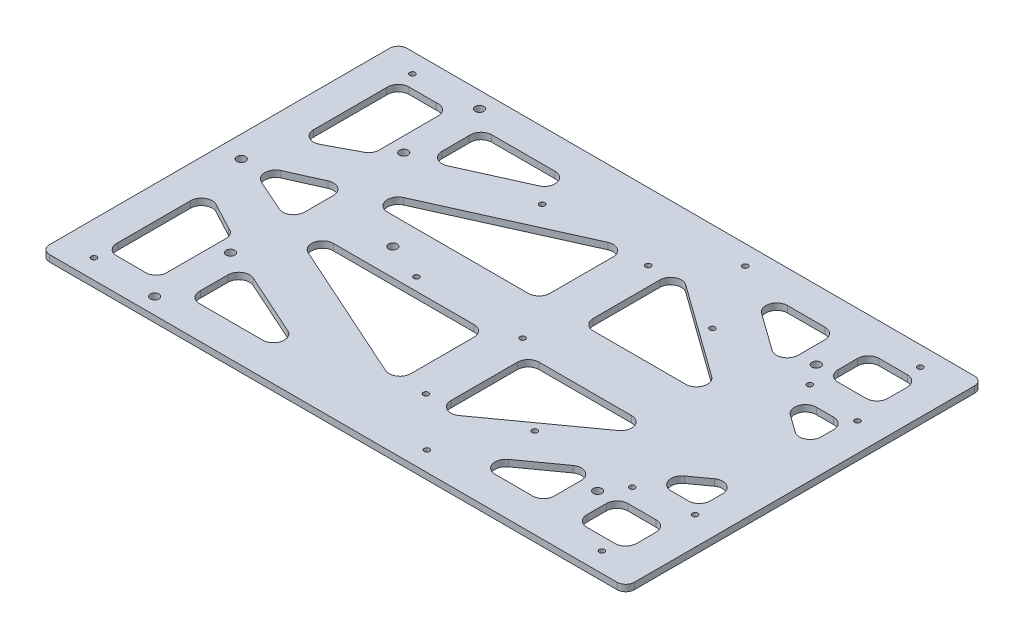
SolidWorks part; units mm, degrees
material "Aleación 1060"
ref_plane "Alzado" through (0, 0, 0) normal (0, 0, 1) x (1, 0, 0)
ref_plane "Planta" through (0, 0, 0) normal (0, 1, 0) x (1, 0, 0)
ref_plane "Vista lateral" through (0, 0, 0) normal (1, 0, 0) x (0, 0, -1)
sketch "Croquis1" plane through (0, 0, 0) normal (0, 1, 0) x (1, 0, 0)
  line L1 (135, -82.5) -> (-135, -82.5)
  line L2 (135, -82.5) -> (135, 82.5)
  line L3 (135, 82.5) -> (-135, 82.5)
  line L4 (-135, -82.5) -> (-135, 82.5)
  line L5 (135, -82.5) -> (-135, 82.5) construction
  line L6 (135, 82.5) -> (-135, -82.5) construction
  point P0 (0, 0)
  dimension "D1" = 165
  dimension "D2" = 270
extrude "Saliente-Extruir1" add sketch "Croquis1" along normal blind 3
fillet "Redondeo1" radius 4 4 edges at (-135, 1.5, -82.5) (135, 1.5, -82.5) (135, 1.5, 82.5) (-135, 1.5, 82.5)
sketch "Croquis2" plane through (0, 3, 0) normal (0, 1, 0) x (1, 0, 0)
  line L0 (131, 82.5) -> (-131, 82.5) construction
  line L1 (135, -78.5) -> (135, 78.5) construction
  circle A0 centre (90, 50.5) radius 2
  dimension "D1" = 4
  dimension "D2" = 32
  dimension "D3" = 45
extrude "Cortar-Extruir1" cut sketch "Croquis2" against normal through all
mirror "Simetría1" about plane through (0, 0, 0) normal (0, 0, 1) of "Cortar-Extruir1"
sketch "Croquis3" plane through (0, 3, 0) normal (0, 1, 0) x (1, 0, 0)
  line L0 (-135, 78.5) -> (-135, -78.5) construction
  line L1 (131, 82.5) -> (-131, 82.5) construction
  line L2 (-135, 0) -> (-113.8944, 0) construction
  circle A0 centre (-90, 75) radius 2
  circle A1 centre (-90, -75) radius 2
  dimension "D1" = 4
  dimension "D2" = 45
  dimension "D3" = 7.5
extrude "Cortar-Extruir2" cut sketch "Croquis3" against normal through all
sketch "Croquis4" plane through (0, 3, 0) normal (0, 1, 0) x (1, 0, 0)
  line L0 (0, 82.5) -> (0, -82.5) construction
  line L1 (131, 82.5) -> (-131, 82.5) construction
  line L2 (-131, -82.5) -> (131, -82.5) construction
  line L3 (-135, 0) -> (135, 0) construction
  line L4 (-135, 78.5) -> (-135, -78.5) construction
  line L5 (135, -78.5) -> (135, 78.5) construction
  line L6 (0, -82.5) -> (131, -82.5) construction
  line L7 (135, -82.5) -> (135, 78.5) construction
  line L8 (131, 82.5) -> (0, 82.5) construction
  line L9 (115, 67.5) -> (102.5, 67.5)
  line L12 (110.2817, 0) -> (2.6409, -64.5845) construction
  line L13 (131, 67.5) -> (-131, 67.5) construction
  line L14 (4.9275, 63.2125) -> (110.2817, 0) construction
  line L15 (15, 10) -> (75.5635, 10)
  line L16 (131, 82.5) -> (-131, 82.5) construction
  line L17 (15, -10) -> (75.5635, -10)
  line L18 (10, 51.3381) -> (10, 15)
  line L19 (17.5725, 55.6256) -> (78.136, 19.2875)
  line L20 (78.136, -19.2875) -> (17.5725, -55.6256)
  line L24 (52.1339, 58.2125) -> (74.9275, 44.5363)
  line L29 (15.2174, 80.3624) -> (149.1548, 0) construction
  line L30 (90, 50.5) -> (90, 67.5) construction
  line L31 (149.1548, 0) -> (12.9308, -81.7344) construction
  line L32 (99.9275, 29.5363) -> (112.4275, 22.0363)
  line L34 (82.5, 62.5) -> (82.5, 48.8238)
  line L36 (97.5, 62.5) -> (97.5, 33.8238)
  line L37 (120, 26.3238) -> (120, 62.5)
  line L38 (77.5, 67.5) -> (54.7063, 67.5)
  line L39 (10, -15) -> (10, -51.3381)
  arc A3 (120, 62.5) -> (115, 67.5) centre (115, 62.5) ccw
  arc A4 (120, 26.3238) -> (112.4275, 22.0363) centre (115, 26.3238) cw
  arc A5 (99.9275, 29.5363) -> (97.5, 33.8238) centre (102.5, 33.8238) cw
  arc A6 (102.5, 67.5) -> (97.5, 62.5) centre (102.5, 62.5) ccw
  arc A7 (10, -51.3381) -> (17.5725, -55.6256) centre (15, -51.3381) ccw
  arc A9 (10, 51.3381) -> (17.5725, 55.6256) centre (15, 51.3381) cw
  arc A10 (75.5635, 10) -> (78.136, 19.2875) centre (75.5635, 15) ccw
  arc A11 (75.5635, -10) -> (78.136, -19.2875) centre (75.5635, -15) cw
  arc A12 (15, 10) -> (10, 15) centre (15, 15) cw
  arc A13 (15, -10) -> (10, -15) centre (15, -15) ccw
  arc A14 (82.5, 48.8238) -> (74.9275, 44.5363) centre (77.5, 48.8238) cw
  arc A15 (77.5, 67.5) -> (82.5, 62.5) centre (77.5, 62.5) cw
  arc A16 (52.1339, 58.2125) -> (54.7063, 67.5) centre (54.7063, 62.5) cw
  point P44 (97.5, 30.9929)
  point P64 (10, -10)
  dimension "D5" = 33.6762
  dimension "D6" = 5
  dimension "D7" = 5
  dimension "D13" = 5
  dimension "D14" = 5
  dimension "D15" = 5
  dimension "D16" = 22.0363
  dimension "D2" = 5
  dimension "D4" = 15
  dimension "D8" = 15
  dimension "D10" = 10
  dimension "D11" = 10
  dimension "D12" = 10
  dimension "D3" = 20
  dimension "D1" = 15
extrude "Cortar-Extruir3" [suppressed] cut sketch "Croquis4" against normal through all
mirror "Simetría4" [suppressed] about plane through (0, 0, 0) normal (1, 0, 0)
sketch "Croquis5" plane through (0, 3, 0) normal (0, 1, 0) x (1, 0, 0)
  line L0 (135, -78.5) -> (135, 78.5) construction
  line L1 (-131, -82.5) -> (131, -82.5) construction
  line L2 (131, 82.5) -> (-131, 82.5) construction
  circle A0 centre (-119.5, 73.5) radius 1.75
  circle A1 centre (34.2, 73.5) radius 1.75
  circle A2 centre (115, 73.5) radius 1.75
  circle A3 centre (115, -73.5) radius 1.75
  circle A4 centre (34.2, -73.5) radius 1.75
  circle A5 centre (-119.5, -73.5) radius 1.75
  point P0 (-119.5, 73.5)
  point P3 (34.2, 73.5)
  point P6 (115, 73.5)
  point P9 (115, -73.5)
  point P12 (34.2, -73.5)
  point P15 (-119.5, -73.5)
  dimension "D1" = 20
  dimension "D2" = 80.8
  dimension "D3" = 153.7
  dimension "D4" = 9
  dimension "D5" = 9
hole_wizard "Taladro roscado M31" positions "Croquis5" profile "Croquis6" tap size "M3" standard "ISO"
sketch "Croquis6" plane through (-119.5, 3, -73.5) normal (1, 0, 0) x (0, 0, 1)
  line L0 (0, 0) -> (0, 9.2511)
  line L1 (0, 9.2511) -> (1.25, 8.5)
  line L2 (1.25, 8.5) -> (1.25, 0)
  line L5 (1.25, 0) -> (0, 0)
  line L10 (0, 9.2511) -> (-1.25, 8.5) construction
  line L11 (0, -6.35) -> (0, 107.95) construction
  dimension "Diámetro de perforador para roscar" = 2.5
  dimension "Profundidad de perforador para roscar" = 8.5
  dimension "Ángulo de perforador" = 118
cosmetic thread "Rosca de taladro1" parameters "D1"=6, "D2"=3
cosmetic thread "Rosca de taladro2" parameters "D1"=6, "D2"=3
cosmetic thread "Rosca de taladro3" parameters "D1"=6, "D2"=3
cosmetic thread "Rosca de taladro4" parameters "D1"=6, "D2"=3
cosmetic thread "Rosca de taladro5" parameters "D1"=6, "D2"=3
cosmetic thread "Rosca de taladro6" parameters "D1"=6, "D2"=3
mirror "Simetría5" [suppressed] about plane through (0, 0, 0) normal (0, 0, 1)
mirror "Simetría7" [suppressed] about plane through (0, 0, 0) normal (1, 0, 0)
mirror "Simetría8" [suppressed] about plane through (0, 0, 0) normal (1, 0, 0)
sketch "Croquis9" plane through (0, 3, 0) normal (0, 1, 0) x (1, 0, 0)
  line L0 (-131, -82.5) -> (131, -82.5) construction
  line L2 (-135, 78.5) -> (-135, -78.5) construction
  line L4 (131, 82.5) -> (-131, 82.5) construction
  circle A0 centre (-125, 0) radius 2
  circle A1 centre (-90, 40) radius 2
  circle A2 centre (-55, 0) radius 2
  circle A3 centre (-90, -40) radius 2
  point P1 (-90, -40)
  point P3 (-55, 0)
  dimension "D1" = 4
  dimension "D5" = 10
  dimension "D3" = 82.5
  dimension "D6" = 45
  dimension "D2" = 42.5
  dimension "D4" = 80
  dimension "D7" = 42.5
extrude "Cortar-Extruir4" cut sketch "Croquis9" against normal blind 4
sketch "Croquis10" plane through (0, 3, 0) normal (0, 1, 0) x (1, 0, 0)
  circle A0 centre (0, 0) radius 2
  circle A1 centre (0, 60.1959) radius 2
  circle A2 centre (0, -65.3126) radius 2
  dimension "D1" = 4
extrude "Cortar-Extruir5" [suppressed] cut sketch "Croquis10" against normal through all
sketch "Croquis11" plane through (0, 3, 0) normal (0, 1, 0) x (1, 0, 0)
  point P0 (-37.4183, 51.3035)
  point P1 (11.5817, 51.3035)
  point P3 (11.5817, -6.6965)
  point P5 (-37.4183, -6.6965)
  point P17 (-37.4183, 51.3035)
  point P19 (-37.4183, -6.6965)
  point P21 (11.5817, -6.6965)
  point P23 (11.5817, 51.3035)
hole_wizard "Taladro roscado M33" positions "Croquis11" profile "Croquis13" tap size "M3" standard "ISO"
sketch "Croquis13" plane through (-37.4183, 3, -51.3035) normal (1, 0, 0) x (0, 0, 1)
  line L0 (0, 0) -> (0, 9.2511)
  line L1 (0, 9.2511) -> (1.25, 8.5)
  line L2 (1.25, 8.5) -> (1.25, 0)
  line L5 (1.25, 0) -> (0, 0)
  line L10 (0, 9.2511) -> (-1.25, 8.5) construction
  line L11 (0, -6.35) -> (0, 107.95) construction
  dimension "Diámetro de perforador para roscar" = 2.5
  dimension "Profundidad de perforador para roscar" = 8.5
  dimension "Ángulo de perforador" = 118
cosmetic thread "Rosca de taladro35" parameters "D1"=6, "D2"=3
cosmetic thread "Rosca de taladro36" parameters "D1"=6, "D2"=3
cosmetic thread "Rosca de taladro37" parameters "D1"=6, "D2"=3
cosmetic thread "Rosca de taladro38" parameters "D1"=6, "D2"=3
sketch "Croquis14" plane through (0, 3, 0) normal (0, 1, 0) x (1, 0, 0)
  line L0 (-135, 0) -> (135, 0) construction
  line L1 (-135, 78.5) -> (-135, -78.5) construction
  line L2 (135, -78.5) -> (135, 78.5) construction
  line L3 (0, 82.5) -> (0, -82.5) construction
  line L5 (-131, -82.5) -> (131, -82.5) construction
  line L6 (-120, 28.3988) -> (-120, 62.0179)
  line L7 (-100.1523, 30.6318) -> (-112.6523, 23.9842)
  line L8 (-96.7551, 61.9356) -> (-96.7099, 34.9641)
  line L9 (131, 67.5) -> (-131, 67.5)
  line L10 (120, 67.5) -> (-120, 67.5) construction
  line L11 (-115, 67.5) -> (-102.5, 67.5)
  line L12 (-120, 78.5) -> (-120, -78.5)
  line L13 (-120, 67.5) -> (-120, -67.5) construction
  line L14 (-77.0591, 67.5) -> (-47.6094, 67.5)
  line L15 (-131, -67.5) -> (131, -67.5)
  line L16 (-120, -67.5) -> (120, -67.5) construction
  line L18 (120, -78.5) -> (120, 78.5)
  line L19 (120, -67.5) -> (120, 33.5) construction
  line L25 (115, 67.5) -> (102.0282, 67.5)
  line L31 (-81.7551, 61.9607) -> (-81.734, 49.3949)
  line L32 (-45.5588, 57.9398) -> (-74.6834, 44.8431)
  line L33 (0, 46.7293) -> (0, 17.5)
  line L35 (-5, 12.5) -> (-70, 12.5)
  line L36 (25, 12.5) -> (67.7096, 12.5)
  line L37 (20, 48.2286) -> (20, 17.5)
  line L38 (27.9201, 52.2873) -> (70.6297, 21.5587)
  line L39 (56.7965, 58.4413) -> (74.1081, 45.986)
  line L40 (90, 50.5) -> (90, 67.5) construction
  line L41 (104.053, 24.4413) -> (112.0799, 18.6662)
  line L42 (82.0282, 62.5) -> (82.0282, 50.0447)
  line L43 (97.0282, 62.5) -> (97.0282, 53.5)
  line L44 (120, 22.7248) -> (120, 28.5)
  line L45 (77.0282, 67.5) -> (59.7166, 67.5)
  line L48 (77.0282, -67.5) -> (59.7166, -67.5)
  line L49 (82.0282, -62.5) -> (82.0282, -50.0447)
  line L50 (56.7965, -58.4413) -> (74.1081, -45.986)
  line L51 (20, -48.2286) -> (20, -17.5)
  line L52 (27.9201, -52.2873) -> (70.6297, -21.5587)
  line L53 (25, -12.5) -> (67.7096, -12.5)
  line L54 (-5, -12.5) -> (-70, -12.5)
  line L56 (0, -46.7293) -> (0, -17.5)
  line L57 (-45.5588, -57.9398) -> (-74.6834, -44.8431)
  line L58 (-81.7551, -61.9607) -> (-81.734, -49.3949)
  line L59 (-77.0591, -67.5) -> (-47.6094, -67.5)
  line L60 (-120, -28.3988) -> (-120, -62.0179)
  line L61 (-100.1523, -30.6318) -> (-112.6523, -23.9842)
  line L62 (-96.7551, -61.9356) -> (-96.7099, -34.9641)
  line L63 (-115, -67.5) -> (-102.5, -67.5)
  line L64 (102.0282, 48.5) -> (115, 48.5)
  line L65 (106.9731, 33.5) -> (115, 33.5)
  line L67 (120, 53.5) -> (120, 62.5)
  line L68 (120, 48.5) -> (120, 67.5) construction
  line L69 (120, -53.5) -> (120, -62.5)
  line L70 (102.0282, -48.5) -> (115, -48.5)
  line L71 (97.0282, -62.5) -> (97.0282, -53.5)
  line L72 (115, -67.5) -> (102.0282, -67.5)
  line L73 (106.9731, -33.5) -> (115, -33.5)
  line L74 (120, -22.7248) -> (120, -28.5)
  line L75 (104.053, -24.4413) -> (112.0799, -18.6662)
  line L76 (-7.0506, 51.2894) -> (-72.0506, 22.0602)
  line L77 (-7.0506, -51.2894) -> (-72.0506, -22.0602)
  arc A10 (-120, 62.0179) -> (-115, 67.5) centre (-115.0233, 62.5001) cw
  arc A11 (-120, 28.3988) -> (-112.6523, 23.9842) centre (-115, 28.3988) ccw
  arc A12 (-100.1523, 30.6318) -> (-96.7099, 34.9641) centre (-101.6918, 35.3889) ccw
  arc A13 (-102.5, 67.5) -> (-96.7551, 61.9356) centre (-101.7157, 62.5619) cw
  arc A14 (-45.5588, 57.9398) -> (-47.6094, 67.5) centre (-47.6094, 62.5) ccw
  arc A15 (-77.0591, 67.5) -> (-81.7551, 61.9607) centre (-76.7851, 62.5075) ccw
  arc A16 (-81.734, 49.3949) -> (-74.6834, 44.8431) centre (-76.734, 49.4032) ccw
  arc A17 (-5, 12.5) -> (0, 17.5) centre (-5, 17.5) ccw
  arc A18 (0, 46.7293) -> (-7.0506, 51.2894) centre (-5, 46.7293) ccw
  arc A19 (-70, 12.5) -> (-72.0506, 22.0602) centre (-70, 17.5) cw
  arc A20 (120, 62.5) -> (115, 67.5) centre (115, 62.5) ccw
  arc A21 (120, 22.7248) -> (112.0799, 18.6662) centre (115, 22.7248) cw
  arc A23 (102.0282, 67.5) -> (97.0282, 62.5) centre (102.0282, 62.5) ccw
  arc A24 (20, 48.2286) -> (27.9201, 52.2873) centre (25, 48.2286) cw
  arc A25 (67.7096, 12.5) -> (70.6297, 21.5587) centre (67.7096, 17.5) ccw
  arc A26 (25, 12.5) -> (20, 17.5) centre (25, 17.5) cw
  arc A27 (82.0282, 50.0447) -> (74.1081, 45.986) centre (77.0282, 50.0447) cw
  arc A28 (77.0282, 67.5) -> (82.0282, 62.5) centre (77.0282, 62.5) cw
  arc A29 (56.7965, 58.4413) -> (59.7166, 67.5) centre (59.7166, 62.5) cw
  arc A34 (56.7965, -58.4413) -> (59.7166, -67.5) centre (59.7166, -62.5) ccw
  arc A35 (77.0282, -67.5) -> (82.0282, -62.5) centre (77.0282, -62.5) ccw
  arc A36 (82.0282, -50.0447) -> (74.1081, -45.986) centre (77.0282, -50.0447) ccw
  arc A37 (25, -12.5) -> (20, -17.5) centre (25, -17.5) ccw
  arc A38 (20, -48.2286) -> (27.9201, -52.2873) centre (25, -48.2286) ccw
  arc A39 (67.7096, -12.5) -> (70.6297, -21.5587) centre (67.7096, -17.5) cw
  arc A40 (-70, -12.5) -> (-72.0506, -22.0602) centre (-70, -17.5) ccw
  arc A41 (0, -46.7293) -> (-7.0506, -51.2894) centre (-5, -46.7293) cw
  arc A42 (-5, -12.5) -> (0, -17.5) centre (-5, -17.5) cw
  arc A43 (-81.734, -49.3949) -> (-74.6834, -44.8431) centre (-76.734, -49.4032) cw
  arc A44 (-77.0591, -67.5) -> (-81.7551, -61.9607) centre (-76.7851, -62.5075) cw
  arc A45 (-45.5588, -57.9398) -> (-47.6094, -67.5) centre (-47.6094, -62.5) cw
  arc A46 (-120, -28.3988) -> (-112.6523, -23.9842) centre (-115, -28.3988) cw
  arc A47 (-100.1523, -30.6318) -> (-96.7099, -34.9641) centre (-101.6918, -35.3889) cw
  arc A48 (-102.5, -67.5) -> (-96.7551, -61.9356) centre (-101.7157, -62.5619) ccw
  arc A49 (-120, -62.0179) -> (-115, -67.5) centre (-115.0233, -62.5001) ccw
  arc A51 (115, 48.5) -> (120, 53.5) centre (115, 53.5) ccw
  arc A52 (102.0282, 48.5) -> (97.0282, 53.5) centre (102.0282, 53.5) cw
  arc A53 (115, 33.5) -> (120, 28.5) centre (115, 28.5) cw
  arc A54 (104.053, 24.4413) -> (106.9731, 33.5) centre (106.9731, 28.5) cw
  arc A55 (115, -48.5) -> (120, -53.5) centre (115, -53.5) cw
  arc A56 (102.0282, -48.5) -> (97.0282, -53.5) centre (102.0282, -53.5) ccw
  arc A57 (102.0282, -67.5) -> (97.0282, -62.5) centre (102.0282, -62.5) cw
  arc A58 (120, -62.5) -> (115, -67.5) centre (115, -62.5) cw
  arc A59 (115, -33.5) -> (120, -28.5) centre (115, -28.5) ccw
  arc A60 (120, -22.7248) -> (112.0799, -18.6662) centre (115, -22.7248) ccw
  arc A61 (104.053, -24.4413) -> (106.9731, -33.5) centre (106.9731, -28.5) ccw
  point P161 (91.4624, 33.5)
  dimension "D6" = 5
  dimension "D7" = 5
  dimension "D8" = 5
  dimension "D9" = 5
  dimension "D11" = 5
  dimension "D24" = 5
  dimension "D25" = 5
  dimension "D26" = 5
  dimension "D13" = 5
  dimension "D27" = 5
  dimension "D18" = 5
  dimension "D28" = 5
  dimension "D5" = 15
  dimension "D10" = 21.86
  dimension "D12" = 20
  dimension "D14" = 0
  dimension "D15" = 15
  dimension "D16" = 39.7752
  dimension "D17" = 12.5
  dimension "D19" = 12.5
  dimension "D21" = 65
  dimension "D1" = 15
  dimension "D2" = 15
  dimension "D3" = 15
  dimension "D4" = 15
extrude "Cortar-Extruir6" cut sketch "Croquis14" against normal through all
mirror "Simetría9" about plane through (0, 0, 0) normal (0, 0, 1) of face at (11.5817, 3, -50.0535)
cosmetic thread "Rosca de taladro39" parameters "D1"=6, "D2"=3
sketch "Croquis15" plane through (0, 3, 0) normal (0, 1, 0) x (1, 0, 0)
  line L0 (0, 0) -> (-135, 0) construction
  line L1 (-135, 78.5) -> (-135, -78.5) construction
  line L2 (0, 0) -> (135, 0) construction
  line L3 (-111.1343, -4.5636) -> (-96.167, -11.264)
  line L4 (-81.734, 49.3949) -> (-81.734, -49.3949) construction
  line L5 (-89.124, 6.7004) -> (-89.124, -6.7004)
  line L6 (-89.124, 49.3949) -> (-89.124, -49.3949) construction
  line L7 (-96.167, 11.264) -> (-111.1343, 4.5636)
  line L11 (135, -78.5) -> (135, 78.5) construction
  arc A1 (-96.167, -11.264) -> (-89.124, -6.7004) centre (-94.124, -6.7004) ccw
  arc A2 (-89.124, 6.7004) -> (-96.167, 11.264) centre (-94.124, 6.7004) ccw
  arc A3 (-111.1343, 4.5636) -> (-111.1343, -4.5636) centre (-109.0914, 0) ccw
  point P22 (-121.3284, 0)
  dimension "D2" = 5
  dimension "D1" = 7.39
extrude "Cortar-Extruir7" cut sketch "Croquis15" against normal through all
sketch "Croquis17" plane through (0, 3, 0) normal (0, 1, 0) x (1, 0, 0)
  circle A0 centre (51.5, 41) radius 1.5
  dimension "D1" = 3
sketch "Croquis19" plane through (0, 3, 0) normal (0, 1, 0) x (1, 0, 0)
  circle A0 centre (96.5, 41) radius 1.5
  circle A1 centre (96.5, -41) radius 1.5
  circle A2 centre (51.5, -41) radius 1.5
  point P0 (96.5, 41)
  point P4 (96.5, -41)
  point P7 (51.5, -41)
  point P10 (51.5, 41)
  dimension "D1" = 3
hole_wizard "Taladro roscado M34" positions "Croquis19" profile "Croquis20" tap size "M3" standard "ISO"
sketch "Croquis20" plane through (96.5, 3, -41) normal (1, 0, 0) x (0, 0, 1)
  line L0 (0, 0) -> (0, 9.2511)
  line L1 (0, 9.2511) -> (1.25, 8.5)
  line L2 (1.25, 8.5) -> (1.25, 0)
  line L5 (1.25, 0) -> (0, 0)
  line L10 (0, 9.2511) -> (-1.25, 8.5) construction
  line L11 (0, -6.35) -> (0, 107.95) construction
  dimension "Diámetro de perforador para roscar" = 2.5
  dimension "Profundidad de perforador para roscar" = 8.5
  dimension "Ángulo de perforador" = 118
cosmetic thread "Rosca de taladro40" parameters "D1"=6, "D2"=3
cosmetic thread "Rosca de taladro41" parameters "D1"=6, "D2"=3
cosmetic thread "Rosca de taladro42" parameters "D1"=6, "D2"=3
cosmetic thread "Rosca de taladro43" parameters "D1"=6, "D2"=3
sketch "Croquis21" plane through (0, 3, 0) normal (0, 1, 0) x (1, 0, 0)
  point P0 (122, 37.5)
  point P1 (122, -37.5)
hole_wizard "Taladro roscado M35" positions "Croquis21" profile "Croquis22" tap size "M3" standard "ISO"
sketch "Croquis22" plane through (122, 3, -37.5) normal (1, 0, 0) x (0, 0, 1)
  line L0 (0, 0) -> (0, 9.2511)
  line L1 (0, 9.2511) -> (1.25, 8.5)
  line L2 (1.25, 8.5) -> (1.25, 0)
  line L5 (1.25, 0) -> (0, 0)
  line L10 (0, 9.2511) -> (-1.25, 8.5) construction
  line L11 (0, -6.35) -> (0, 107.95) construction
  dimension "Diámetro de perforador para roscar" = 2.5
  dimension "Profundidad de perforador para roscar" = 8.5
  dimension "Ángulo de perforador" = 118
cosmetic thread "Rosca de taladro44" parameters "D1"=6, "D2"=3
cosmetic thread "Rosca de taladro45" parameters "D1"=6, "D2"=3
